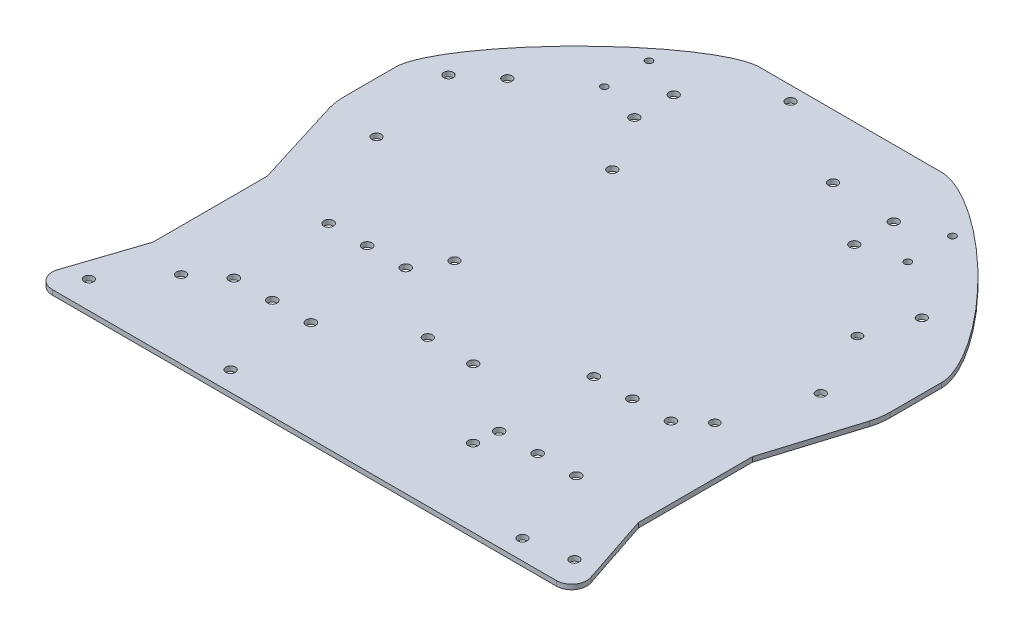
SolidWorks part; units mm, degrees
ref_plane "Front Plane" through (0, 0, 0) normal (0, 0, 1) x (1, 0, 0)
ref_plane "Top Plane" through (0, 0, 0) normal (0, 1, 0) x (1, 0, 0)
ref_plane "Right Plane" through (0, 0, 0) normal (1, 0, 0) x (0, 0, -1)
sketch "Sketch1" plane through (0, 0, 0) normal (0, 1, 0) x (1, 0, 0)
  line L0 (-90, 180) -> (-90, 0) construction
  line L1 (-180, 180) -> (0, 180)
  line L2 (-180, 180) -> (-180, 0)
  line L3 (-180, 0) -> (0, 0)
  line L4 (0, 180) -> (0, 0)
  line L5 (-180, 90) -> (0, 90) construction
  line L6 (-180, 30) -> (0, 30)
  line L7 (-130, 30) -> (-50, 30)
  line L8 (-130, 30) -> (-130, -30)
  line L9 (-130, -30) -> (-50, -30)
  line L10 (-50, 30) -> (-50, -30)
  line L11 (-130, 30) -> (-50, -30) construction
  line L12 (-130, -30) -> (-50, 30) construction
  dimension "D1" = 180
  dimension "D2" = 180
  dimension "D3" = 60
  dimension "D4" = 80
extrude "Boss-Extrude1" add sketch "Sketch1" along normal blind 1.6 contours L10 L3 L8 L9 | L2 L6 L4 L1 | L6 L10 L3 L4 | L8 L6 L2 L3 | L10 L6 L8 L3 region at (-90, 0, -105) region at (-155, 0, -15) region at (-25, 0, -15) region at (-90, 0, -15) region at (-90, 0, 15)
sketch "Sketch2" plane through (0, 1.6, 0) normal (0, 1, 0) x (1, 0, 0)
  line L0 (-180, 30) -> (0, 30)
  line L1 (-180, 180) -> (-180, 0) construction
  line L2 (0, 180) -> (0, 0) construction
  line L3 (-180, 180) -> (0, 180) construction
  line L4 (-90, 180) -> (-90, -30) construction
  line L5 (-130, -30) -> (-50, -30) construction
  dimension "D1" = 150
sketch "Sketch3" plane through (0, 1.6, 0) normal (0, 1, 0) x (1, 0, 0)
  line L0 (-180, 122) -> (0, 122)
  line L1 (-180, 180) -> (-180, 0) construction
  line L2 (0, 180) -> (0, 0) construction
  line L3 (-180, 30) -> (0, 30) construction
  dimension "D1" = 92
sketch "Sketch5" plane through (0, 1.6, 0) normal (0, 1, 0) x (1, 0, 0)
  line L0 (-114, 180) -> (-114, -30)
  line L1 (-180, 180) -> (0, 180) construction
  line L2 (-130, -30) -> (-50, -30) construction
  line L3 (-90, 180) -> (-90, -30) construction
  dimension "D1" = 24
fillet "Fillet1" radius 60 2 edges at (0, 0.8, -180) (-180, 0.8, -180) conic rho 0.2
sketch "Sketch6" plane through (0, 1.6, 0) normal (0, 1, 0) x (1, 0, 0)
  line L0 (-50, 0) -> (-130, 0)
  line L1 (-130, 0) -> (-130, -30)
  line L2 (-130, -30) -> (-50, -30)
  line L3 (-50, -30) -> (-50, 0)
  line L4 (-180, 0) -> (-170, 30.1113)
  line L5 (-170, 30.1113) -> (-170, 67.7113)
  line L6 (-170, 67.7113) -> (-180, 100)
  line L7 (-180, 120) -> (-180, 0) construction
  line L8 (-90, 180) -> (-90, -30) construction
  line L10 (-90, 180) -> (-90, 0) construction
  line L11 (0, 0) -> (-10, 30.1113)
  line L12 (-10, 30.1113) -> (-10, 67.7113)
  line L13 (-10, 67.7113) -> (0, 100)
  line M3 (0, 0) -> (0, 120)
  line M7 (-180, 120) -> (-180, 0)
  line M9 (-130, 0) -> (-130, -30)
  line M10 (-130, -30) -> (-50, -30)
  line M11 (-50, -30) -> (-50, 0)
  dimension "D1" = 37.6
  dimension "D2" = 80
  dimension "D3" = 100
extrude "Cut-Extrude1" cut sketch "Sketch6" against normal blind 10 contours L0 M11 M9 M10 | L5 L6 L4 M7 | L13 L12 L11 M3 region at (-90, 1.6, 15) region at (-175.7558, 1.6, -49.5379) region at (-4.2442, 1.6, -49.5379)
fillet "Fillet2" radius 5 2 edges at (-180, 0.8, 0) (0, 0.8, 0)
fillet "Fillet3" radius 20 2 edges at (-180, 0.8, -100) (0, 0.8, -100)
sketch "Sketch8" plane through (0, 1.6, 0) normal (0, 1, 0) x (1, 0, 0)
  circle A4 centre (-105.105, 175.3311) radius 1.55
  circle A5 centre (-74.9002, 159.1312) radius 1.55
  circle A8 centre (-115, 74.5) radius 1.55
  circle A9 centre (-115, 126.5) radius 1.55
  circle A11 centre (-146.4125, 64.417) radius 1.5875
  circle A12 centre (-133.7125, 64.417) radius 1.5875
  circle A13 centre (-121.0125, 64.417) radius 1.5875
  circle A14 centre (-146.4125, 33.175) radius 1.5875
  circle A15 centre (-133.7125, 33.175) radius 1.5875
  circle A16 centre (-121.0125, 33.175) radius 1.5875
  circle A17 centre (-58.9875, 64.417) radius 1.5875
  circle A18 centre (-46.2875, 64.417) radius 1.5875
  circle A19 centre (-33.5875, 64.417) radius 1.5875
  circle A20 centre (-33.5875, 33.175) radius 1.5875
  circle A21 centre (-46.2875, 33.175) radius 1.5875
  circle A22 centre (-58.9875, 33.175) radius 1.5875
  circle A23 centre (-59.9, 25.5) radius 1.55
  circle A24 centre (-24.6, 6.5) radius 1.55
  circle A25 centre (-120.8, 6.5) radius 1.55
  circle A26 centre (-156.1, 25.5) radius 1.55
  circle A27 centre (-27.14, 119.392) radius 1.5
  circle A28 centre (-25.87, 71.132) radius 1.5
  circle A29 centre (-169, 126.5) radius 1.55
  circle A30 centre (-126.25, 145) radius 1.55
  circle A31 centre (-53.75, 145) radius 1.55
  circle A32 centre (-170, 9) radius 1.55
  circle A33 centre (-10, 9) radius 1.55
  dimension "D3" = 3.1
  dimension "D4" = 3.1
  dimension "D5" = 3.1
  dimension "D6" = 3.1
  dimension "D7" = 3.1
  dimension "D8" = 3.175
  dimension "D9" = 3.175
  dimension "D10" = 3.175
  dimension "D11" = 3.175
  dimension "D12" = 3.175
  dimension "D13" = 3.175
  dimension "D14" = 3.1
  dimension "D15" = 3.1
  dimension "D16" = 3.1
  dimension "D17" = 3.1
  dimension "D18" = 3.175
  dimension "D19" = 3.175
  dimension "D20" = 3.175
  dimension "D21" = 3.175
  dimension "D22" = 3.175
  dimension "D23" = 3.175
  dimension "D24" = 3
  dimension "D25" = 3
  dimension "D26" = 3.1
  dimension "D27" = 3.1
  dimension "D28" = 3.1
  dimension "D29" = 3.1
extrude "Cut-Extrude2" cut sketch "Sketch8" against normal up to next (1.6 mm away)
sketch "Sketch9" plane through (0, 0, 0) normal (0, -1, 0) x (1, 0, 0)
  line L0 (-90, -180) -> (-90, 30) construction
  circle A0 centre (-163.2, -97) radius 1.55
  circle A1 centre (-158.3, -135.2) radius 1.55
  circle A2 centre (-126.25, -158) radius 1.55
  circle A3 centre (-53.75, -158) radius 1.55
  circle A4 centre (-21.7, -135.2) radius 1.55
  circle A5 centre (-16.8, -97) radius 1.55
  circle A10 centre (-140, -148.857) radius 1.143
  circle A11 centre (-140, -163.589) radius 1.143
  circle A12 centre (-40, -148.857) radius 1.143
  circle A13 centre (-40, -163.589) radius 1.143
  circle A14 centre (-97.5, -48.175) radius 1.55
  circle A15 centre (-82.5, -48.175) radius 1.55
  circle A16 centre (-121.0125, -33.175) radius 1.5875 construction
  dimension "D1" = 3.1
  dimension "D2" = 3.1
  dimension "D3" = 3.1
  dimension "D4" = 3.1
  dimension "D5" = 3.1
  dimension "D6" = 3.1
  dimension "D11" = 2.286
  dimension "D12" = 2.286
  dimension "D13" = 2.286
  dimension "D14" = 2.286
  dimension "D15" = 3.1
  dimension "D16" = 3.1
  dimension "D17" = 15
  dimension "D19" = 15
  dimension "D18" = 7.5
extrude "Cut-Extrude3" cut sketch "Sketch9" against normal up to next
